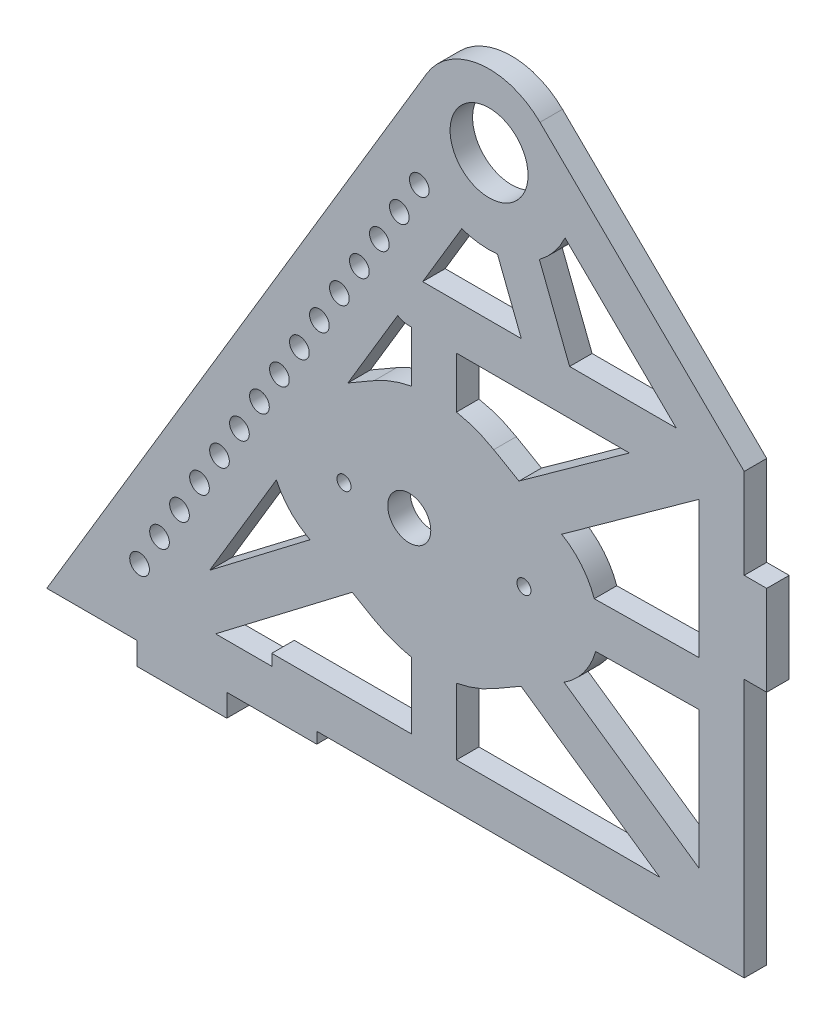
SolidWorks part; units mm, degrees
ref_plane "Front Plane" through (0, 0, 0) normal (0, 0, 1) x (1, 0, 0)
ref_plane "Top Plane" through (0, 0, 0) normal (0, 1, 0) x (1, 0, 0)
ref_plane "Right Plane" through (0, 0, 0) normal (1, 0, 0) x (0, 0, -1)
sketch "Sketch2" plane through (0, 0, 0) normal (0, 0, 1) x (1, 0, 0)
  line L1 (50.8, 6.35) -> (76.2, 6.35)
  line L2 (0, 6.35) -> (107.2144, 185.7594)
  line L4 (76.2, 6.35) -> (76.2, 9.525)
  line L6 (0, 6.35) -> (0, 0)
  line L7 (0, 0) -> (25.4, 0) construction
  line L8 (25.4, 6.35) -> (25.4, 0)
  line L13 (76.2, 9.525) -> (83.9864, 9.525)
  line L17 (0, -29.7981) -> (203.2, -29.7981) construction
  line L20 (196.85, 9.525) -> (196.85, 82.55)
  line L22 (196.85, 133.35) -> (139.2046, 189.8844)
  line L23 (196.85, 107.95) -> (196.85, 133.35)
  line L24 (196.85, 107.95) -> (203.2, 107.95)
  line L26 (196.85, 82.55) -> (203.2, 82.55)
  line L27 (203.2, 107.95) -> (203.2, 82.55)
  line L28 (83.9864, 9.525) -> (196.85, 9.525)
  line L29 (0, 6.35) -> (25.4, 6.35)
  line L30 (25.4, 0) -> (50.8, 0)
  line L31 (50.8, 0) -> (50.8, 6.35)
  arc A0 (139.2046, 189.8844) -> (107.2144, 185.7594) centre (124.8331, 175.2305) ccw
  circle A1 centre (124.8331, 175.2305) radius 11 construction
  circle A2 centre (124.8331, 175.2305) radius 4 construction
  circle A3 centre (124.8331, 175.2305) radius 11
  dimension "D3" = 22
  dimension "D4" = 9.525
  dimension "D5" = 8
  dimension "D6" = 22
  dimension "D1" = 168.8805
  dimension "D2" = 124.8331
  dimension "D7" = 6.35
  dimension "D8" = 25.4
  dimension "D9" = 3.175
  dimension "D10" = 6.35
  dimension "D11" = 73.025
  dimension "D12" = 203.2
  dimension "D13" = 76.2
  dimension "D14" = 6.35
  dimension "D15" = 25.4
  dimension "D16" = 6.35
  dimension "D17" = 25.4
  dimension "D18" = 25.4
extrude "Boss-Extrude1" add sketch "Sketch2" along normal blind 6.35 contours L22 A0 L2 L29 L8 L30 L31 L1 L4 L13 L28 L20 L26 L27 L24 L23 A3 region at (118.2801, 80.4306, 0)
sketch "Sketch4" [suppressed] plane through (0, 0, 6.35) normal (0, 0, 1) x (1, 0, 0)
  line L0 (1673.3123, 156.2334) -> (1577.5737, -3.9728)
  line L1 (1691.5051, 171.4226) -> (1750.822, 113.2489)
  line L2 (1684.7881, 175.4367) -> (1577.5737, -3.9728) construction
  line L3 (1590.9538, 18.4171) -> (1750.822, 18.4171)
  line L4 (1686.3016, 73.3904) -> (1617.2071, 143.6449) construction
  line L7 (1681.7742, 68.9378) -> (1612.6797, 139.1923)
  line L10 (1690.8289, 77.843) -> (1621.7344, 148.0975)
  line L13 (1566.672, 2.5421) -> (1566.672, -3.8079)
  line L14 (1566.672, -3.8079) -> (1592.072, -3.8079)
  line L15 (1592.072, -3.8079) -> (1592.072, 2.5421)
  line L16 (1592.072, 2.5421) -> (1642.872, 2.5421)
  line L17 (1642.872, 2.5421) -> (1642.872, 5.7171)
  line L18 (1642.872, 5.7171) -> (1763.522, 5.7171)
  line L24 (1763.522, 5.7171) -> (1763.522, 78.7421)
  line L25 (1673.8864, 181.9515) -> (1566.672, 2.5421)
  line L26 (1566.672, 2.5421) -> (1566.672, -3.8079)
  line L27 (1566.672, -3.8079) -> (1592.072, -3.8079)
  line L28 (1592.072, -3.8079) -> (1592.072, 2.5421)
  line L29 (1592.072, 2.5421) -> (1642.872, 2.5421)
  line L30 (1642.872, 2.5421) -> (1642.872, 5.7171)
  line L31 (1642.872, 5.7171) -> (1763.522, 5.7171)
  line L38 (1673.8864, 181.9515) -> (1566.672, 2.5421)
  line L39 (1686.3016, 73.3904) -> (1776.688, 147.3217) construction
  line L42 (1682.2812, 78.3056) -> (1772.6676, 152.2368)
  line L45 (1690.3219, 68.4752) -> (1780.7084, 142.4065)
  line L46 (1686.3016, 73.3904) -> (1535.3984, -21.6576) construction
  line L47 (1750.822, 113.2489) -> (1750.822, 18.4171)
  line L48 (1689.6858, 68.0174) -> (1538.7827, -27.0307)
  line L49 (1682.9173, 78.7634) -> (1532.0142, -16.2846)
  line L50 (1686.3016, 73.3904) -> (1767.8024, 12.8123) construction
  line L51 (1690.0896, 78.4868) -> (1771.5905, 17.9087)
  line L52 (1682.5135, 68.294) -> (1764.0144, 7.7159)
  line L53 (1691.5051, 171.4226) -> (1681.8948, -9.6316) construction
  line L54 (1697.8462, 171.086) -> (1688.2358, -9.9682)
  line L55 (1685.1641, 171.7592) -> (1675.5537, -9.2951)
  line L60 (1763.522, 5.7171) -> (1763.522, 78.7421)
  line L61 (1763.522, 129.5421) -> (1705.8766, 186.0765)
  line L62 (1763.522, 129.5421) -> (1705.8766, 186.0765)
  line L68 (1763.522, 78.7421) -> (1769.872, 78.7421)
  line L69 (1763.522, 78.7421) -> (1769.872, 78.7421)
  line L70 (1769.872, 78.7421) -> (1769.872, 104.1421)
  line L71 (1769.872, 78.7421) -> (1769.872, 104.1421)
  line L72 (1769.872, 104.1421) -> (1763.522, 104.1421)
  line L73 (1769.872, 104.1421) -> (1763.522, 104.1421)
  line L74 (1763.522, 104.1421) -> (1763.522, 129.5421)
  line L75 (1763.522, 104.1421) -> (1763.522, 129.5421)
  arc A1 (1705.8766, 186.0765) -> (1673.8864, 181.9515) centre (1691.5051, 171.4226) ccw
  arc A2 (1705.8766, 186.0765) -> (1673.8864, 181.9515) centre (1691.5051, 171.4226) ccw
  circle A4 centre (1691.5051, 171.4226) radius 23.7
  circle A5 centre (1691.5051, 171.4226) radius 23.7
  arc A14 (1681.7742, 68.9378) -> (1690.8289, 77.843) centre (1686.3016, 73.3904) ccw
  arc A15 (1621.7344, 148.0975) -> (1612.6797, 139.1923) centre (1617.2071, 143.6449) ccw
  arc A16 (1682.2812, 78.3056) -> (1690.3219, 68.4752) centre (1686.3016, 73.3904) ccw
  arc A17 (1780.7084, 142.4065) -> (1772.6676, 152.2368) centre (1776.688, 147.3217) ccw
  arc A18 (1689.6858, 68.0174) -> (1682.9173, 78.7634) centre (1686.3016, 73.3904) ccw
  arc A19 (1532.0142, -16.2846) -> (1538.7827, -27.0307) centre (1535.3984, -21.6576) ccw
  arc A20 (1690.0896, 78.4868) -> (1682.5135, 68.294) centre (1686.3016, 73.3904) ccw
  arc A21 (1764.0144, 7.7159) -> (1771.5905, 17.9087) centre (1767.8024, 12.8123) ccw
  arc A22 (1697.8462, 171.086) -> (1685.1641, 171.7592) centre (1691.5051, 171.4226) ccw
  arc A23 (1675.5537, -9.2951) -> (1688.2358, -9.9682) centre (1681.8948, -9.6316) ccw
  point P15 (1651.7543, 108.5176)
  point P28 (1731.4948, 110.356)
  point P35 (1610.85, 25.8664)
  point P42 (1727.052, 43.1013)
  point P50 (1686.6999, 80.8955)
  dimension "D6" = 6.35
  dimension "D4" = 12.7
  dimension "D5" = 12.7
  dimension "D1" = 0
  dimension "D2" = 12.7
  dimension "D3" = 12.7
extrude "Cut-Extrude1" [suppressed] cut sketch "Sketch4" against normal through all contours L49 L7 L0 | A5 L0 L10 L55 | A5 L54 L42 L1 | L45 L51 L47 L1 | L52 L54 L3 | L55 L48 L3
fillet "Fillet1" [suppressed] radius 2.54
sketch "Sketch5" plane through (0, 0, 6.35) normal (0, 0, 1) x (1, 0, 0)
  arc A0 (107.7056, 77.303) -> (97.4063, 78.1479) centre (102.3066, 74.6857) ccw construction
  arc A1 (107.7056, 77.303) -> (97.4063, 78.1479) centre (102.3066, 74.6857) ccw construction
  arc A2 (107.7056, 77.303) -> (97.4063, 78.1479) centre (102.3066, 74.6857) cw construction
  arc A3 (107.7742, 77.3363) -> (97.344, 78.1919) centre (102.3066, 74.6857) cw
  arc A4 (107.7742, 77.3363) -> (97.344, 78.1919) centre (102.3066, 74.6857) ccw
  dimension "D1" = 0.0762
extrude "Cut-Extrude2" cut sketch "Sketch5" against normal through all both and the other way through all
sketch "Sketch6" plane through (0, 0, 0) normal (0, 0, -1) x (-1, 0, 0)
  circle A0 centre (-83.8831, 74.1134) radius 1.9844 construction
  circle A1 centre (-134.6831, 74.1134) radius 1.9844 construction
  circle A2 centre (-83.8831, 74.1134) radius 1.9844
  circle A3 centre (-134.6831, 74.1134) radius 1.9844
extrude "Cut-Extrude3" cut sketch "Sketch6" against normal through all both and the other way through all
sketch "Sketch8" plane through (0, 0, 0) normal (0, 0, -1) x (-1, 0, 0)
  line L0 (-101.5018, 151.4426) -> (-26.1791, 25.4) construction
  line L1 (0, 6.35) -> (-107.2144, 185.7594) construction
  line L2 (0, 6.35) -> (-25.4, 6.35) construction
  circle A0 centre (-105.1401, 157.5309) radius 2.7781
  circle A1 centre (-99.5, 148.093) radius 2.7781
  circle A2 centre (-93.86, 138.6551) radius 2.7781
  circle A3 centre (-88.2199, 129.2171) radius 2.7781
  circle A4 centre (-82.5798, 119.7792) radius 2.7781
  circle A5 centre (-76.9398, 110.3413) radius 2.7781
  circle A6 centre (-71.2997, 100.9034) radius 2.7781
  circle A7 centre (-65.6596, 91.4655) radius 2.7781
  circle A8 centre (-60.0196, 82.0275) radius 2.7781
  circle A9 centre (-54.3795, 72.5896) radius 2.7781
  circle A10 centre (-48.7394, 63.1517) radius 2.7781
  circle A11 centre (-43.0994, 53.7138) radius 2.7781
  circle A12 centre (-37.4593, 44.2758) radius 2.7781
  circle A13 centre (-31.8192, 34.8379) radius 2.7781
  circle A14 centre (-26.1791, 25.4) radius 2.7781
  circle A17 centre (-124.8331, 175.2305) radius 23.7
  circle A18 centre (-124.8331, 175.2305) radius 23.7 construction
  point P7 (-106.0477, 159.0497)
  point P35 (-27.5881, 27.7578)
  dimension "D2" = 5.5562
  dimension "D1" = 12.7
  dimension "D5" = 19.05
  dimension "D4" = 12.7
  dimension "D3" = 15
extrude "Cut-Extrude5" cut sketch "Sketch8" against normal through all
sketch "Sketch7" plane through (0, 0, 0) normal (0, 0, -1) x (-1, 0, 0)
  line L0 (-109.2831, 74.1134) -> (-109.2831, 22.225) construction
  line L3 (-102.9331, 74.1134) -> (-102.9331, 22.225)
  line L4 (-138.8522, 66.8967) -> (-119.8078, 55.8949) construction
  line L5 (-119.8078, 92.3319) -> (-138.8522, 81.3301) construction
  line L6 (-79.7141, 81.3301) -> (-98.7585, 92.3319) construction
  line L7 (-98.7585, 55.8949) -> (-79.7141, 66.8967) construction
  line L8 (-145.205, 55.8998) -> (-126.1606, 44.898)
  line L9 (-92.4057, 44.898) -> (-73.3613, 55.8998)
  line L10 (-73.3613, 92.327) -> (-92.4057, 103.3288)
  line L11 (-126.1606, 103.3288) -> (-145.205, 92.327)
  line L14 (-115.6331, 74.1134) -> (-115.6331, 22.225)
  line L17 (-109.2831, 74.1134) -> (-37.1793, 19.05) construction
  line L20 (-105.4291, 79.1601) -> (-33.3253, 24.0967)
  line L23 (-113.1372, 69.0667) -> (-41.0334, 14.0033)
  line L26 (-109.2831, 74.1134) -> (-184.15, 22.225) construction
  line L29 (-105.666, 68.8943) -> (-180.5328, 17.006)
  line L32 (-112.9003, 79.3324) -> (-187.7672, 27.444)
  line L35 (-109.2831, 74.1134) -> (-184.15, 128.017) construction
  line L36 (-130.3121, 180.8172) -> (-184.15, 128.017)
  line L37 (-184.15, 128.017) -> (-184.15, 22.225)
  line L38 (-184.15, 22.225) -> (-63.5, 22.225)
  line L39 (-63.5, 22.225) -> (-63.5, 19.05)
  line L40 (-63.5, 19.05) -> (-22.3844, 19.05)
  line L41 (-22.3844, 19.05) -> (-118.1161, 179.2446)
  line L42 (-130.3121, 180.8172) -> (-184.15, 128.017)
  line L43 (-184.15, 128.017) -> (-184.15, 22.225)
  line L44 (-184.15, 22.225) -> (-63.5, 22.225)
  line L45 (-63.5, 22.225) -> (-63.5, 19.05)
  line L46 (-63.5, 19.05) -> (-22.3844, 19.05)
  line L50 (-112.9935, 68.9601) -> (-187.8603, 122.8637)
  line L54 (-37.1793, 19.05) -> (-117.1202, 152.8207)
  line L55 (0, 6.35) -> (-107.2144, 185.7594) construction
  line L56 (-105.5728, 79.2666) -> (-180.4397, 133.1702)
  line L57 (-109.2831, 74.1134) -> (-184.15, 75.121) construction
  line L58 (-109.3686, 67.764) -> (-184.2355, 68.7716)
  line L59 (-109.1977, 80.4628) -> (-184.0645, 81.4704)
  line L60 (-184.15, 128.017) -> (-102.2976, 128.017) construction
  line L61 (-184.15, 134.367) -> (-102.2976, 134.367)
  line L62 (-184.15, 121.667) -> (-102.2976, 121.667)
  line L63 (-124.8331, 175.2305) -> (-143.2238, 128.017) construction
  line L64 (-118.9162, 172.9258) -> (-137.3068, 125.7122)
  line L65 (-130.7501, 177.5353) -> (-149.1408, 130.3217)
  line L66 (-109.2831, 74.1134) -> (-109.2831, 121.667) construction
  line L67 (-115.6331, 74.1134) -> (-115.6331, 121.667)
  line L68 (-102.9331, 74.1134) -> (-102.9331, 121.667)
  circle A0 centre (-124.8331, 175.2305) radius 11
  circle A1 centre (-124.8331, 175.2305) radius 23.7
  arc A2 (-118.1161, 179.2446) -> (-130.3121, 180.8172) centre (-124.8331, 175.2305) ccw
  arc A4 (-138.8522, 81.3301) -> (-138.8522, 66.8967) centre (-134.6831, 74.1134) ccw construction
  arc A6 (-79.7141, 66.8967) -> (-79.7141, 81.3301) centre (-83.8831, 74.1134) ccw construction
  arc A8 (-119.8078, 92.3319) -> (-98.7585, 92.3319) centre (-109.2831, 74.1134) cw construction
  arc A9 (-119.8078, 55.8949) -> (-98.7585, 55.8949) centre (-109.2831, 74.1134) ccw construction
  arc A10 (-126.1606, 44.898) -> (-92.4057, 44.898) centre (-109.2831, 74.1134) ccw
  arc A11 (-73.3613, 55.8998) -> (-73.3613, 92.327) centre (-83.8831, 74.1134) ccw
  arc A12 (-126.1606, 103.3288) -> (-92.4057, 103.3288) centre (-109.2831, 74.1134) cw
  arc A13 (-145.205, 92.327) -> (-145.205, 55.8998) centre (-134.6831, 74.1134) ccw
  arc A36 (-102.9331, 74.1134) -> (-115.6331, 74.1134) centre (-109.2831, 74.1134) ccw
  arc A37 (-115.6331, 22.225) -> (-102.9331, 22.225) centre (-109.2831, 22.225) ccw
  arc A38 (-105.4291, 79.1601) -> (-113.1372, 69.0667) centre (-109.2831, 74.1134) ccw
  arc A39 (-41.0334, 14.0033) -> (-33.3253, 24.0967) centre (-37.1793, 19.05) ccw
  arc A40 (-105.666, 68.8943) -> (-112.9003, 79.3324) centre (-109.2831, 74.1134) ccw
  arc A41 (-187.7672, 27.444) -> (-180.5328, 17.006) centre (-184.15, 22.225) ccw
  arc A42 (-112.9935, 68.9601) -> (-105.5728, 79.2666) centre (-109.2831, 74.1134) ccw
  arc A43 (-180.4397, 133.1702) -> (-187.8603, 122.8637) centre (-184.15, 128.017) ccw
  arc A44 (-109.3686, 67.764) -> (-109.1977, 80.4628) centre (-109.2831, 74.1134) ccw
  arc A45 (-184.0645, 81.4704) -> (-184.2355, 68.7716) centre (-184.15, 75.121) ccw
  arc A46 (-184.15, 134.367) -> (-184.15, 121.667) centre (-184.15, 128.017) ccw
  arc A47 (-102.2976, 121.667) -> (-102.2976, 134.367) centre (-102.2976, 128.017) ccw
  arc A48 (-118.9162, 172.9258) -> (-130.7501, 177.5353) centre (-124.8331, 175.2305) ccw
  arc A49 (-149.1408, 130.3217) -> (-137.3068, 125.7122) centre (-143.2238, 128.017) ccw
  arc A50 (-115.6331, 74.1134) -> (-102.9331, 74.1134) centre (-109.2831, 74.1134) ccw
  arc A51 (-102.9331, 121.667) -> (-115.6331, 121.667) centre (-109.2831, 121.667) ccw
  point P28 (-109.2831, 48.1692)
  point P35 (-73.2312, 46.5817)
  point P41 (-146.7166, 48.1692)
  point P49 (-146.7166, 101.0652)
  point P60 (-146.7166, 74.6172)
  point P67 (-143.2238, 128.017)
  point P72 (-134.0285, 151.6237)
  point P80 (-109.2831, 97.8902)
  dimension "D3" = 22
  dimension "D5" = 6.35
  dimension "D6" = 25.4
  dimension "D1" = 12.7
  dimension "D2" = 12.7
  dimension "D4" = 12.7
extrude "Cut-Extrude4" cut sketch "Sketch7" against normal blind 50.8 contours A1 L42 L61 L65 | A1 L64 L61 L54 | L11 A12 L67 L62 L56 | A45 L59 A13 L50 L43 | A13 L58 L43 L32 | A10 L8 L29 L44 L14 | A10 L3 L44 L45 L46 L23 L9 | A11 L9 L20 L54 | A47 L62 L68 A12 L10 L54 region at (82.03, 31.433, 0) region at (61.3449, 51.0797, 0) region at (96.6831, 111.2016, 0) region at (137.5592, 32.2407, 0) region at (134.9118, 113.4356, 0) region at (169.8713, 54.0134, 0) region at (120.7556, 141.8155, 0) region at (169.6774, 95.7143, 0) region at (154.6845, 145.9667, 0)
